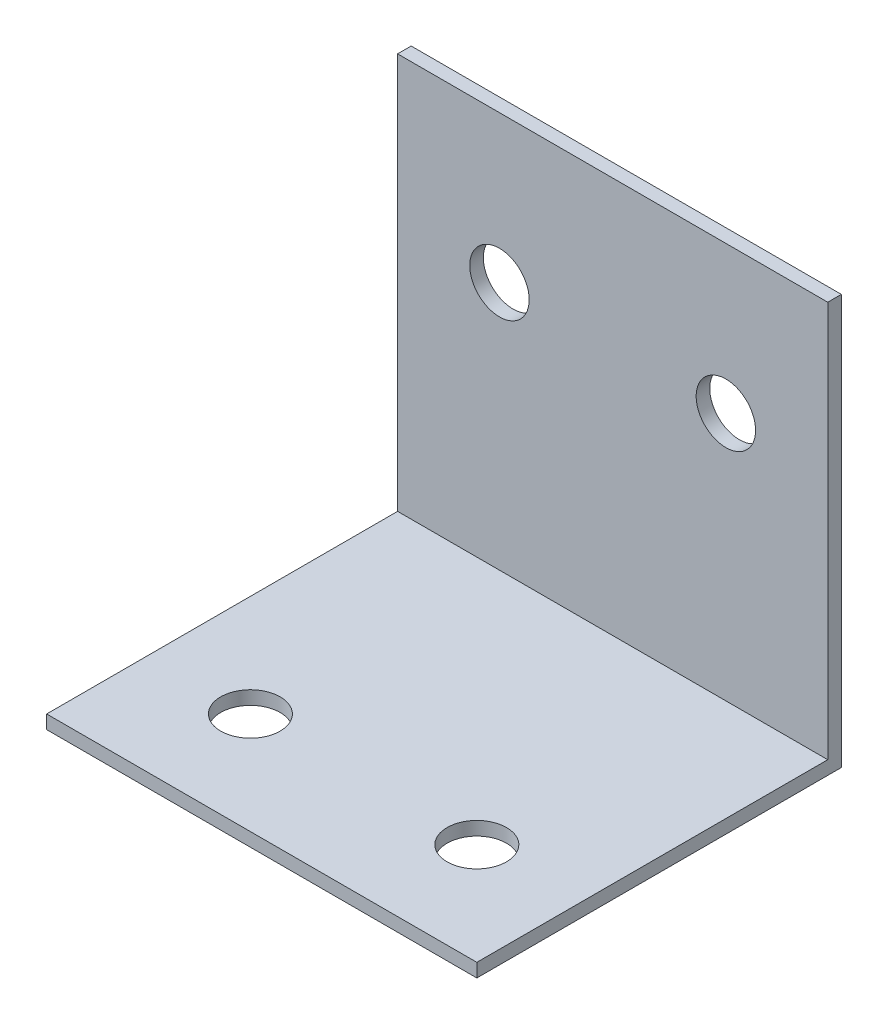
SolidWorks part; units mm, degrees
ref_plane "Front Plane" through (0, 0, 0) normal (0, 0, 1) x (1, 0, 0)
ref_plane "Top Plane" through (0, 0, 0) normal (0, 1, 0) x (1, 0, 0)
ref_plane "Right Plane" through (0, 0, 0) normal (1, 0, 0) x (0, 0, -1)
sketch "Sketch1" plane through (0, 0, 0) normal (0, 1, 0) x (1, 0, 0)
  line L0 (-19, 0) -> (-19, -32.2) construction
  line L1 (0, 0) -> (-38, 0)
  line L2 (0, 0) -> (0, -32.2)
  line L3 (0, -32.2) -> (-38, -32.2)
  line L4 (-38, 0) -> (-38, -32.2)
  circle A0 centre (-29, -23.2) radius 2.625
  circle A2 centre (-9, -23.2) radius 2.625
  dimension "D3" = 5.25
  dimension "D4" = 9
  dimension "D5" = 10
  dimension "D6" = 9
  dimension "D1" = 32.2
  dimension "D2" = 38
extrude "Boss-Extrude1" add sketch "Sketch1" along normal blind 1.2
sketch "Sketch2" plane through (0, 1.2, 0) normal (0, 1, 0) x (1, 0, 0)
  line L0 (0, -32.2) -> (0, 0) construction
  line L1 (-38, 0) -> (0, 0)
  line L2 (-38, 0) -> (-38, -1.2)
  line L3 (-38, -1.2) -> (0, -1.2)
  line L4 (0, 0) -> (0, -1.2)
  dimension "D1" = 1.2
extrude "Boss-Extrude2" add sketch "Sketch2" along normal blind 35
sketch "Sketch3" plane through (0, 0, 1.2) normal (0, 0, 1) x (1, 0, 0)
  line L0 (-19, 36.2) -> (-19, 1.2) construction
  line L1 (-38, 36.2) -> (0, 36.2) construction
  line L2 (-38, 1.2) -> (0, 1.2) construction
  line L5 (-38, 1.2) -> (0, 1.2) construction
  circle A4 centre (-29, 23.2) radius 2.625
  circle A5 centre (-9, 23.2) radius 2.625
  dimension "D1" = 5.25
  dimension "D2" = 22
  dimension "D3" = 10
extrude "Cut-Extrude1" cut sketch "Sketch3" against normal through all
